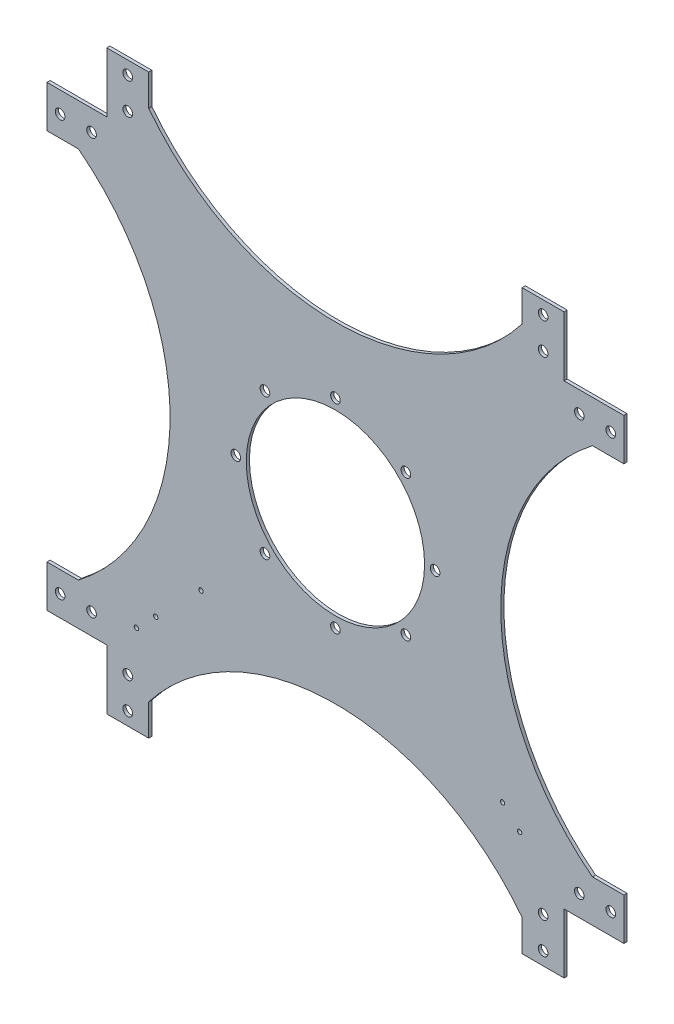
SolidWorks part; units mm, degrees
ref_plane "Front Plane" through (0, 0, 0) normal (0, 0, 1) x (1, 0, 0)
ref_plane "Top Plane" through (0, 0, 0) normal (0, 1, 0) x (1, 0, 0)
ref_plane "Right Plane" through (0, 0, 0) normal (1, 0, 0) x (0, 0, -1)
sketch "Sketch1" plane through (0, 0, 0) normal (0, 0, 1) x (1, 0, 0)
  line L0 (0, 0) -> (367.2182, 0) construction
  line L1 (0, 0) -> (0, -316.5866) construction
  line L2 (0, 0) -> (218, 218) construction
  line L3 (0, 0) -> (218, -218) construction
  line L4 (218, 218) -> (218, 275)
  line L5 (218, 218) -> (275, 218)
  line L6 (218, 275) -> (178, 275)
  line L7 (178, 275) -> (178, 245)
  line L8 (0, 0) -> (-218, 218) construction
  line L9 (0, 0) -> (-218, -218) construction
  line L10 (0, 0) -> (-199.7109, 0) construction
  line L11 (-218, 218) -> (-218, 275)
  line L12 (-218, 275) -> (-178, 275)
  line L13 (-178, 275) -> (-178, 245)
  line L14 (218, -218) -> (275, -218)
  line L15 (275, -218) -> (275, -178)
  line L16 (275, -178) -> (245, -178)
  line L17 (275, 218) -> (275, 178)
  line L18 (275, 178) -> (245, 178)
  line L19 (218, -218) -> (218, -275)
  line L20 (218, -275) -> (178, -275)
  line L21 (178, -275) -> (178, -245)
  line L22 (-178, -275) -> (-178, -245)
  line L23 (-218, -275) -> (-178, -275)
  line L24 (-218, -218) -> (-218, -275)
  line L25 (-218, -218) -> (-275, -218)
  line L26 (-275, -218) -> (-275, -178)
  line L27 (-275, -178) -> (-245, -178)
  line L28 (-275, 178) -> (-245, 178)
  line L29 (-275, 218) -> (-275, 178)
  line L30 (-218, 218) -> (-275, 218)
  circle A0 centre (0, 0) radius 85
  arc A1 (-178, 245) -> (178, 245) centre (0, 382.6263) ccw
  arc A2 (245, 178) -> (245, -178) centre (382.6263, 0) ccw
  arc A3 (-178, -245) -> (178, -245) centre (0, -382.6263) cw
  arc A4 (-245, 178) -> (-245, -178) centre (-382.6263, 0) cw
  dimension "D4" = 170
  dimension "D9" = 225
  dimension "D1" = 45
  dimension "D3" = 57
  dimension "D5" = 40
  dimension "D6" = 45
  dimension "D7" = 45
  dimension "D8" = 30
  dimension "D10" = 275
sheet metal parameters "Sheet-Metal1" thickness 3 parameters "D1"=1
base flange "Base-Flange1" sketch "Sketch1" thickness 3 reverse thickness direction yes parameters "D1"=1
sketch "Sketch2" plane through (0, 0, 3) normal (0, 0, 1) x (1, 0, 0)
  line L0 (218, 218) -> (218, 275) construction
  line L1 (218, 275) -> (178, 275) construction
  line L2 (275, 178) -> (275, 218) construction
  line L3 (275, 218) -> (218, 218) construction
  line L4 (0, 0) -> (260.8486, 0) construction
  line L5 (0, 0) -> (0, -250.4708) construction
  circle A0 centre (198, 262.5) radius 4.6
  circle A1 centre (198, 232.5) radius 4.6
  circle A2 centre (232.5, 198) radius 4.6
  circle A3 centre (262.5, 198) radius 4.6
  circle A4 centre (262.5, -198) radius 4.6
  circle A5 centre (232.5, -198) radius 4.6
  circle A6 centre (198, -232.5) radius 4.6
  circle A7 centre (198, -262.5) radius 4.6
  circle A8 centre (-198, -262.5) radius 4.6
  circle A9 centre (-198, -232.5) radius 4.6
  circle A10 centre (-232.5, -198) radius 4.6
  circle A11 centre (-262.5, -198) radius 4.6
  circle A12 centre (-262.5, 198) radius 4.6
  circle A13 centre (-232.5, 198) radius 4.6
  circle A14 centre (-198, 232.5) radius 4.6
  circle A15 centre (-198, 262.5) radius 4.6
  point P8 (218, 246.5)
  dimension "D2" = 9.2
  dimension "D1" = 20
  dimension "D3" = 12.5
  dimension "D4" = 30
  dimension "D5" = 30
  dimension "D6" = 12.5
  dimension "D7" = 20
extrude "Extrude1" cut sketch "Sketch2" against normal blind 3 normal cut yes
sketch "Sketch3" plane through (0, 0, 3) normal (0, 0, 1) x (1, 0, 0)
  line L0 (0, 0) -> (220.4396, 0) construction
  line L1 (0, 0) -> (0, -219.5819) construction
  line L2 (0, 0) -> (178.1909, 178.1909) construction
  circle A0 centre (0, 0) radius 95 construction
  circle A1 centre (0, 95) radius 4.6
  circle A2 centre (-95, 0) radius 4.6 construction
  circle A3 centre (0, -95) radius 4.6 construction
  circle A4 centre (95, 0) radius 4.6 construction
  dimension "D2" = 9.2
  dimension "D3" = 190
  dimension "D1" = 45
extrude "Extrude2" cut sketch "Sketch3" against normal blind 3 normal cut yes
pattern_circular "CirPattern1" count 8 over 360 about axis through (0, 0, 3) along (0, 0, 1) of "Extrude2"
sketch "Sketch4" plane through (0, 0, 3) normal (0, 0, 1) x (1, 0, 0)
  line L0 (-218, -218) -> (0, 0) construction
  line L1 (0, 0) -> (218, -218) construction
  line L2 (218, -218) -> (275, -218) construction
  circle A0 centre (-189.7157, -189.7157) radius 2.1
  circle A1 centre (-171.331, -171.331) radius 2.1
  circle A2 centre (-128.1974, -128.1974) radius 2.1
  circle A3 centre (175.5736, -175.5736) radius 2.1
  circle A4 centre (159.3101, -159.3101) radius 2.1
  dimension "D1" = 4.2
  dimension "D2" = 26
  dimension "D3" = 87
  dimension "D4" = 40
  dimension "D5" = 23
  dimension "D6" = 60
extrude "Cut-Extrude1" cut sketch "Sketch4" against normal blind 3 normal cut yes
flat pattern "Flat-Pattern1" [suppressed]
sketch "Bend-Lines1" plane through (0, 0, 0) normal (0, 1, 0) x (-1, 0, 0)
